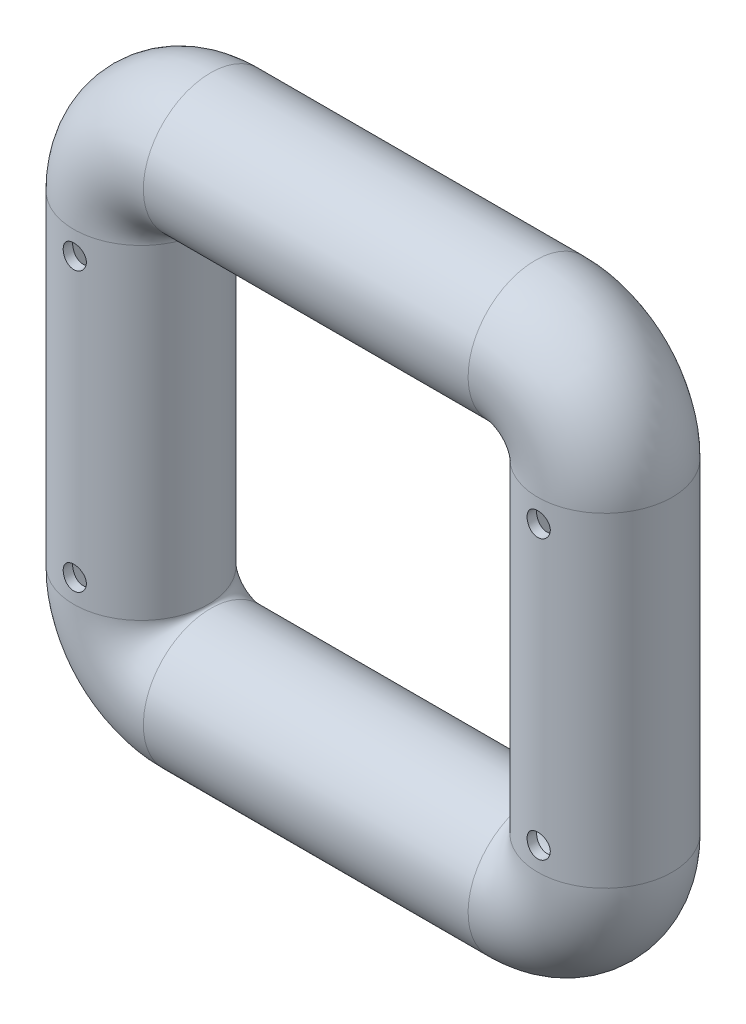
SolidWorks part; units mm, degrees
ref_plane "Plan de face" through (0, 0, 0) normal (0, 0, 1) x (1, 0, 0)
ref_plane "Plan de dessus" through (0, 0, 0) normal (0, 1, 0) x (1, 0, 0)
ref_plane "Plan de droite" through (0, 0, 0) normal (1, 0, 0) x (0, 0, -1)
sketch "Esquisse1" plane through (0, 0, 0) normal (0, 0, 1) x (1, 0, 0)
  line L1 (-35, 50) -> (35, 50)
  line L2 (-50, 35) -> (-50, -35)
  line L3 (-35, -50) -> (35, -50)
  line L4 (50, 35) -> (50, -35)
  line L5 (-50, 50) -> (50, -50) construction
  line L6 (-50, -50) -> (50, 50) construction
  arc A0 (35, -50) -> (50, -35) centre (35, -35) ccw
  arc A1 (-50, -35) -> (-35, -50) centre (-35, -35) ccw
  arc A2 (35, 50) -> (50, 35) centre (35, 35) cw
  arc A3 (-35, 50) -> (-50, 35) centre (-35, 35) ccw
  point P0 (0, 0)
  dimension "D3" = 15
  dimension "D1" = 100
  dimension "D2" = 100
sweep "Balayage-Mince1" add path "Esquisse1" circular profile diameter 29 parameters "D1"=2, "D3"=29
sketch "Esquisse24" plane through (0, 0, 0) normal (0, 0, 1) x (1, 0, 0)
  line L0 (0, 0) -> (-64.5, 0) construction
  line L1 (-64.5, 35) -> (-64.5, -35) construction
  line L2 (-50, 35) -> (-50, -35) construction
  line L3 (-35.5, 35) -> (-64.5, 35) construction
  line L4 (-35.5, -35) -> (-64.5, -35) construction
  line L5 (0, 35) -> (0, -35) construction
  circle A0 centre (-50, 30) radius 2.5
  circle A1 centre (-50, -30) radius 2.5
  circle A2 centre (50, 30) radius 2.5
  circle A3 centre (50, -30) radius 2.5
  point P18 (0, 0)
  dimension "D2" = 5
  dimension "D1" = 30
extrude "Enlèv. mat.-Extru.1" cut sketch "Esquisse24" against normal through all and the other way through all
